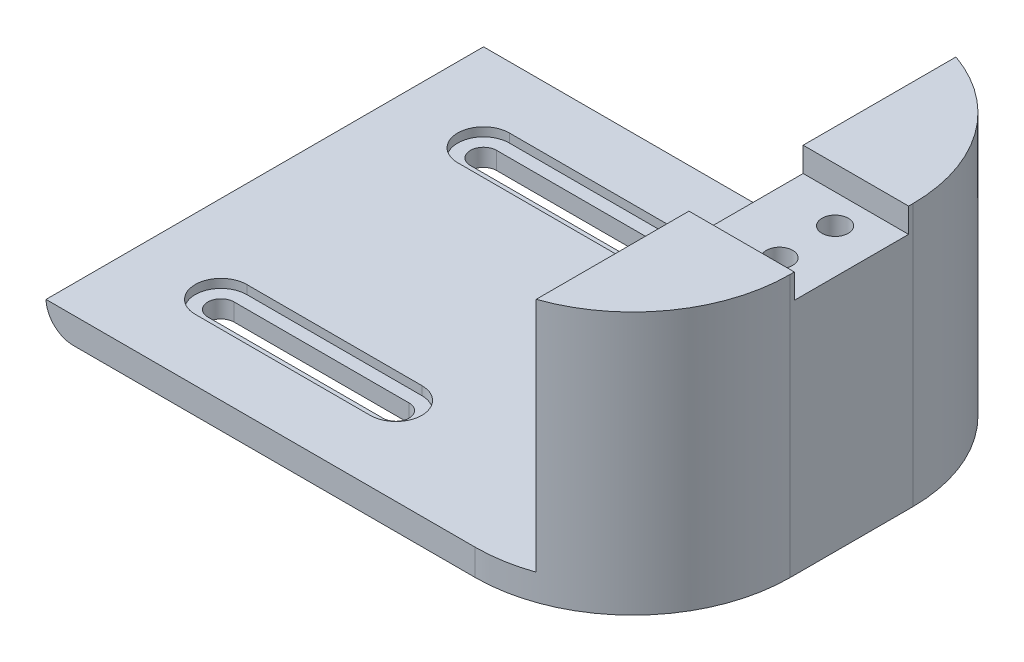
SolidWorks part; units mm, degrees
ref_plane "Front Plane" through (0, 0, 0) normal (0, 0, 1) x (1, 0, 0)
ref_plane "Top Plane" through (0, 0, 0) normal (0, 1, 0) x (1, 0, 0)
ref_plane "Right Plane" through (0, 0, 0) normal (1, 0, 0) x (0, 0, -1)
sketch "ProfileSketch1" plane through (0, 0, 0) normal (0, 0, 1) x (1, 0, 0)
  line L1 (67.05, 0) -> (67.05, -3)
  line L2 (67.05, -3) -> (0, -3)
  line L3 (0, -3) -> (0, 0)
  line L4 (0, 0) -> (55, 0)
  line L5 (55, 0) -> (55, 27)
  line L6 (55, 27) -> (67.05, 27)
  line L7 (67.05, 27) -> (67.05, 0)
  dimension "D2" = 3
  dimension "D3" = 27
  dimension "D4" = 12.05
  dimension "D1" = 55
extrude "Boss-Extrude1" add sketch "ProfileSketch1" along normal blind 50
sketch "MountHolesSketch2" plane through (0, 0, 0) normal (0, 1, 0) x (1, 0, 0)
  line L0 (55, 0) -> (0, 0) construction
  line L1 (55, -50) -> (0, -50) construction
  line L2 (0, -50) -> (0, 0) construction
  line L3 (55, -50) -> (55, 0) construction
  line L4 (10, -8.5) -> (30, -8.5)
  line L5 (10, -11.5) -> (30, -11.5)
  line L6 (10, -38.5) -> (30, -38.5)
  line L7 (10, -41.5) -> (30, -41.5)
  line L8 (45, -16) -> (45, -34)
  arc A0 (10, -8.5) -> (10, -11.5) centre (10, -10) ccw
  arc A1 (10, -38.5) -> (10, -41.5) centre (10, -40) ccw
  arc A2 (45, -34) -> (45, -16) centre (45, -25) ccw
  arc A4 (30, -11.5) -> (30, -8.5) centre (30, -10) ccw
  arc A5 (30, -41.5) -> (30, -38.5) centre (30, -40) ccw
  dimension "D1" = 3
  dimension "D6" = 18
  dimension "D2" = 10
  dimension "D3" = 10
  dimension "D4" = 10
  dimension "D5" = 10
  dimension "D7" = 25
  dimension "D8" = 20
extrude "MountHolesCut-Extrude1" cut sketch "MountHolesSketch2" against normal through all
sketch "MicroSwitchCutSketch3" plane through (0, 27, 0) normal (0, 1, 0) x (1, 0, 0)
  line L0 (55, -50) -> (55, 0) construction
  line L1 (55, -18.475) -> (67.05, -18.475)
  line L2 (55, -18.475) -> (55, -31.525)
  line L3 (55, -31.525) -> (67.05, -31.525)
  line L4 (67.05, -18.475) -> (67.05, -31.525)
  line L5 (67.05, -50) -> (67.05, 0) construction
  line L6 (67.05, 0) -> (55, 0) construction
  dimension "D1" = 13.05
  dimension "D2" = 18.475
extrude "MicroSwitchCut-Extrude2" cut sketch "MicroSwitchCutSketch3" against normal blind 2.8
sketch "MicroSwitchMountingHolesSketch4" plane through (0, 24.2, 0) normal (0, 1, 0) x (1, 0, 0)
  line L0 (55, -31.525) -> (67.05, -31.525) construction
  line L1 (67.05, -18.475) -> (55, -18.475) construction
  line L2 (55, -50) -> (55, 0) construction
  circle A0 centre (62, -28.175) radius 1.5
  circle A1 centre (62, -21.825) radius 1.5
  dimension "D4" = 3
  dimension "D1" = 3.35
  dimension "D2" = 3.35
  dimension "D3" = 7
extrude "MicroSwitchMountingHolesCut-Extrude3" cut sketch "MicroSwitchMountingHolesSketch4" against normal blind 3
fillet "RailEdgeFillet1" radius 3.125 1 edges at (0, -3, 25)
fillet "FrontEdgeFillet1" radius 18 2 edges at (67.05, 12, 0) (67.05, 12, 50)
sketch "M3ButtonHeadCutSketch1" plane through (0, 0, 0) normal (0, 1, 0) x (1, 0, 0)
  line L0 (10, -10) -> (30, -10) construction
  line L1 (10, -7.05) -> (30, -7.05)
  line L2 (10, -12.95) -> (30, -12.95)
  line L3 (10, -40) -> (30, -40) construction
  line L4 (10, -37.05) -> (30, -37.05)
  line L5 (10, -42.95) -> (30, -42.95)
  arc A0 (10, -7.05) -> (10, -12.95) centre (10, -10) ccw
  arc A1 (30, -12.95) -> (30, -7.05) centre (30, -10) ccw
  arc A2 (10, -37.05) -> (10, -42.95) centre (10, -40) ccw
  arc A3 (30, -42.95) -> (30, -37.05) centre (30, -40) ccw
  point P4 (20, -10)
  point P9 (20, -40)
  dimension "D1" = 5.9
extrude "Cut-Extrude1" cut sketch "M3ButtonHeadCutSketch1" against normal blind 1
equation "\"M3ScrewDiameter\"= 3mm"
equation "\"D1@MountHolesSketch2\" = \"M3ScrewDiameter\""
equation "\"YAxisMicroSwitchBlockWidth\"= 50mm"
equation "\"MicroSwitchLength\" = 13.05mm"
equation "\"MicroSwitchTerminalHeight\"= 3.5mm"
equation "\"MicroSwitchDepth\"= 2.8mm"
equation "\"MicroSwitchMountHoleOffsetFromSide\"= 3.35mm"
equation "\"MicroSwitchMountHoleOffsetFromBottom\"= 1.5mm"
equation "\"MicroSwitchExtraMountingHeight\"= 2mm"
equation "\"D1@Boss-Extrude1\"=\"YAxisMicroSwitchBlockWidth\""
equation "\"D7@MountHolesSketch2\" = \"YAxisMicroSwitchBlockWidth\" / 2"
equation "\"D1@MicroSwitchCutSketch3\" = \"MicroSwitchLength\""
equation "\"D2@MicroSwitchCutSketch3\" = \"YAxisMicroSwitchBlockWidth\" / 2 - \"MicroSwitchLength\" / 2"
equation "\"D1@MicroSwitchCut-Extrude2\" = \"MicroSwitchDepth\""
equation "\"D1@MicroSwitchMountingHolesSketch4\" = \"MicroSwitchMountHoleOffsetFromSide\""
equation "\"D2@MicroSwitchMountingHolesSketch4\" = \"MicroSwitchMountHoleOffsetFromSide\""
equation "\"D3@MicroSwitchMountingHolesSketch4\"=\"MicroSwitchExtraMountingHeight\" + \"MicroSwitchTerminalHeight\" + \"MicroSwitchMountHoleOffsetFromBottom\""
equation "\"M3HeatInsertHoleDiameter\"= 3mm'Spec"
equation "\"D4@MicroSwitchMountingHolesSketch4\" = \"M3HeatInsertHoleDiameter\""
equation "\"M3HeatInsertHoleDepth\"= 4mm"
equation "\"YAxisMicroSwitchMountingBlockHeight\"= 27mm"
equation "\"YAxisMicroSwitchSupportHeight\"= 3mm"
equation "\"D2@ProfileSketch1\"=\"YAxisMicroSwitchSupportHeight\""
equation "\"D3@ProfileSketch1\"=\"YAxisMicroSwitchMountingBlockHeight\""
equation "\"D4@ProfileSketch1\"=\"MicroSwitchExtraMountingHeight\" + \"MicroSwitchTerminalHeight\" + 6.55mm"
equation "\"MicroSwitchHeight\"= 6.55mm"
equation "\"M2HeatInsertDepth\"=3"
equation "\"D1@MicroSwitchMountingHolesCut-Extrude3\" = \"M2HeatInsertDepth\""
equation "\"MicroSwitchCableClampHoleDiameter\"=18"
equation "\"M3ButtonHeadDiameter\"=5.9"
equation "\"D1@M3ButtonHeadCutSketch1\" = \"M3ButtonHeadDiameter\""
